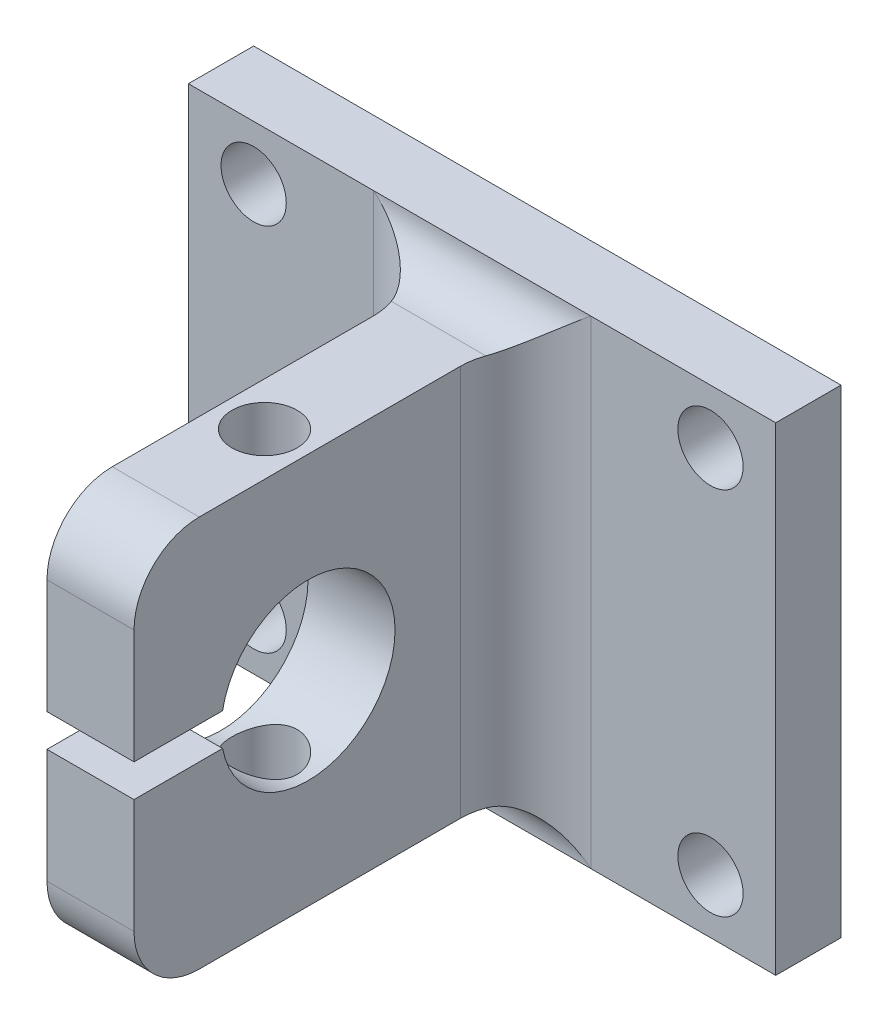
SolidWorks part; units mm, degrees
ref_plane "Front Plane" through (0, 0, 0) normal (0, 0, 1) x (1, 0, 0)
ref_plane "Top Plane" through (0, 0, 0) normal (0, 1, 0) x (1, 0, 0)
ref_plane "Right Plane" through (0, 0, 0) normal (1, 0, 0) x (0, 0, -1)
sketch "Sketch1" plane through (0, 0, 0) normal (0, 0, 1) x (1, 0, 0)
  line L1 (-13.5, -11) -> (13.5, -11)
  line L2 (-13.5, -11) -> (-13.5, 11)
  line L3 (-13.5, 11) -> (13.5, 11)
  line L4 (13.5, -11) -> (13.5, 11)
  line L5 (-13.5, -11) -> (13.5, 11) construction
  line L6 (-13.5, 11) -> (13.5, -11) construction
  line L7 (-10.5, -8.5) -> (-10.5, 8.5) construction
  line L8 (-10.5, 8.5) -> (10.5, 8.5) construction
  circle A5 centre (-10.5, -8.5) radius 1.5
  circle A6 centre (-10.5, 8.5) radius 1.5
  circle A7 centre (10.5, 8.5) radius 1.5
  circle A8 centre (10.5, -8.5) radius 1.5
  point P0 (0, 0)
  point P11 (-13.5, 0)
  point P12 (0, 11)
  point P13 (-10.5, 0)
  point P21 (0, 8.5)
  dimension "D5" = 3
  dimension "D1" = 27
  dimension "D2" = 22
  dimension "D6" = 17
  dimension "D7" = 21
extrude "Boss-Extrude1" add sketch "Sketch1" along normal blind 3
sketch "Sketch2" plane through (0, 0, 3) normal (0, 0, 1) x (1, 0, 0)
  line L1 (-2, 9) -> (2, 9)
  line L2 (-2, 9) -> (-2, -9)
  line L3 (-2, -9) -> (2, -9)
  line L4 (2, 9) -> (2, -9)
  line L5 (-13.5, -11) -> (13.5, -11) construction
  line L6 (2, 3.6093) -> (-2, 3.6093) construction
  line L7 (-13.5, 11) -> (-13.5, -11) construction
  point P4 (-13.5, 0)
  point P10 (0, -11)
  point P11 (0, 3.6093)
  point P16 (-2, 0)
  dimension "D1" = 4
  dimension "D2" = 18
extrude "Boss-Extrude2" add sketch "Sketch2" along normal blind 18
sketch "Sketch3" plane through (2, 0, 0) normal (1, 0, 0) x (0, 0, -1)
  line L0 (-21, -9) -> (-21, 9) construction
  line L1 (-3, -9) -> (-3, 9) construction
  circle A0 centre (-13, 0) radius 4
  point P5 (-21, 0)
  dimension "D1" = 8
  dimension "D2" = 10
extrude "Cut-Extrude1" cut sketch "Sketch3" against normal through all both and the other way through all
sketch "Sketch4" plane through (2, 0, 0) normal (1, 0, 0) x (0, 0, -1)
  line L1 (-22.3796, -0.75) -> (-14.282, -0.75)
  line L2 (-22.3796, -0.75) -> (-22.3796, 0.75)
  line L3 (-22.3796, 0.75) -> (-14.282, 0.75)
  line L4 (-14.282, -0.75) -> (-14.282, 0.75)
  line L5 (-21, -9) -> (-21, 9) construction
  point P6 (-21, 0)
  point P7 (-22.3796, 0)
  dimension "D1" = 1.5
extrude "Cut-Extrude2" cut sketch "Sketch4" against normal through all both and the other way through all
sketch "Sketch5" plane through (0, 11, 0) normal (0, 1, 0) x (1, 0, 0)
  line L0 (2, -21) -> (-2, -21) construction
  line L2 (2, -3) -> (-2, -3) construction
  circle A0 centre (0, -13) radius 1.5
  point P5 (0, -21)
  dimension "D1" = 3
  dimension "D2" = 10
fillet "Fillet1" radius 3 2 edges at (-2, 0, 3) (2, 0, 3)
extrude "Cut-Extrude3" cut sketch "Sketch5" against normal through all both and the other way through all
fillet "Fillet2" radius 2 2 edges at (0, 9, 3) (0, -9, 3)
fillet "Fillet3" radius 3 2 edges at (0, -9, 21) (0, 9, 21)
